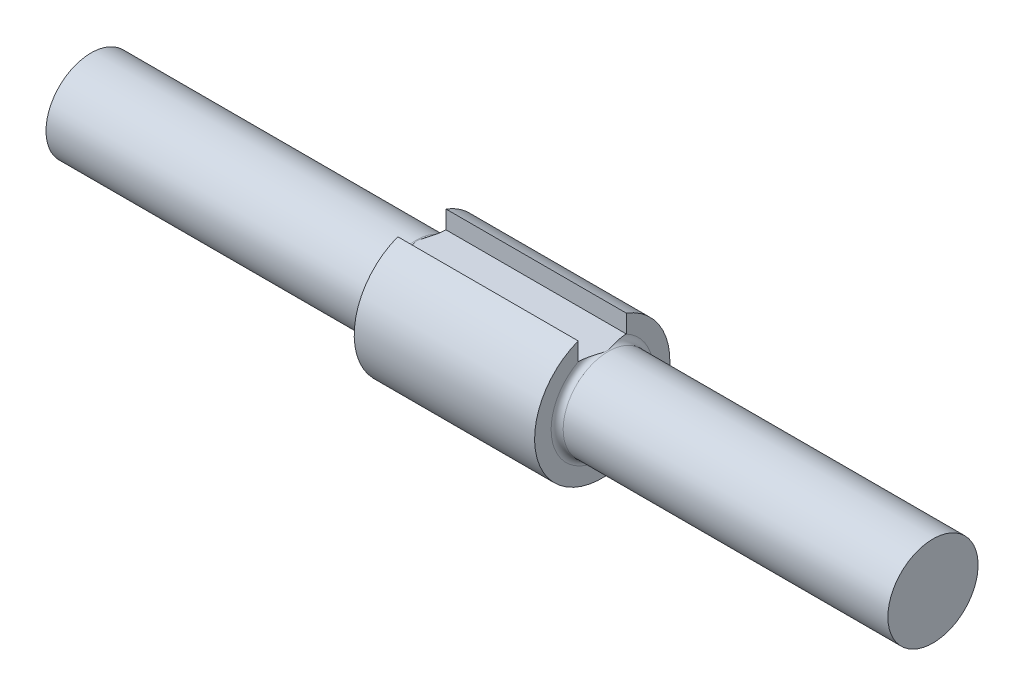
SolidWorks part; units mm, degrees
ref_plane "Front Plane" through (0, 0, 0) normal (0, 0, 1) x (1, 0, 0)
ref_plane "Top Plane" through (0, 0, 0) normal (0, 1, 0) x (1, 0, 0)
ref_plane "Right Plane" through (0, 0, 0) normal (1, 0, 0) x (0, 0, -1)
sketch "Sketch1" plane through (0, 0, 0) normal (0, 0, 1) x (1, 0, 0)
  line L0 (0, 0) -> (70, 0)
  line L1 (70, 0) -> (70, 7.5)
  line L2 (70, 7.5) -> (15, 7.5)
  line L3 (15, 7.5) -> (15, 11.25)
  line L4 (15, 11.25) -> (-15, 11.25)
  line L5 (-15, 11.25) -> (-15, 7.5)
  line L6 (-15, 7.5) -> (-70, 7.5)
  line L7 (-70, 7.5) -> (-70, 0)
  line L8 (-70, 0) -> (0, 0)
  dimension "D1" = 70
  dimension "D2" = 70
  dimension "D3" = 7.5
  dimension "D4" = 7.5
  dimension "D5" = 55
  dimension "D6" = 55
  dimension "D7" = 11.25
revolve "Revolve1" add sketch "Sketch1" angle 360 about L0
sketch "Sketch4" plane through (0, 0, 0) normal (1, 0, 0) x (0, 0, -1)
  line L0 (0, 0) -> (0, 11.25)
  line L1 (4, 10.5149) -> (0, 10.5149)
  line L2 (0, 10.5149) -> (-4, 10.5149)
  line L3 (4, 10.5149) -> (4, 7.5149)
  line L4 (4, 7.5149) -> (-4, 7.5149)
  line L5 (-4, 7.5149) -> (-4, 10.5149)
  circle A0 centre (0, 0) radius 11.25 construction
  circle A1 centre (0, 0) radius 11.25
  dimension "D1" = 4
  dimension "D2" = 3
extrude "Cut-Extrude1" cut sketch "Sketch4" against normal through all and the other way through all contours L4 L3 L1 L0 | L5 L4 L0 L2 | L1 A1 L0 | L0 A1 L2 region at (0, 10.8098, 1.5068) region at (0, 9.0149, -2) region at (0, 10.8098, -1.5068) region at (0, 9.0149, 2)
fillet "Fillet5" radius 1 1 edges at (-15, 0, 7.5) type face fillet first side face at (-15, 0, 7.5) second side face at (-70, 0, 7.5)
fillet "Fillet6" radius 1 1 edges at (15, 0, 7.5) type face fillet first side face at (15, 0, 7.5) second side face at (15, 0, 7.5)
